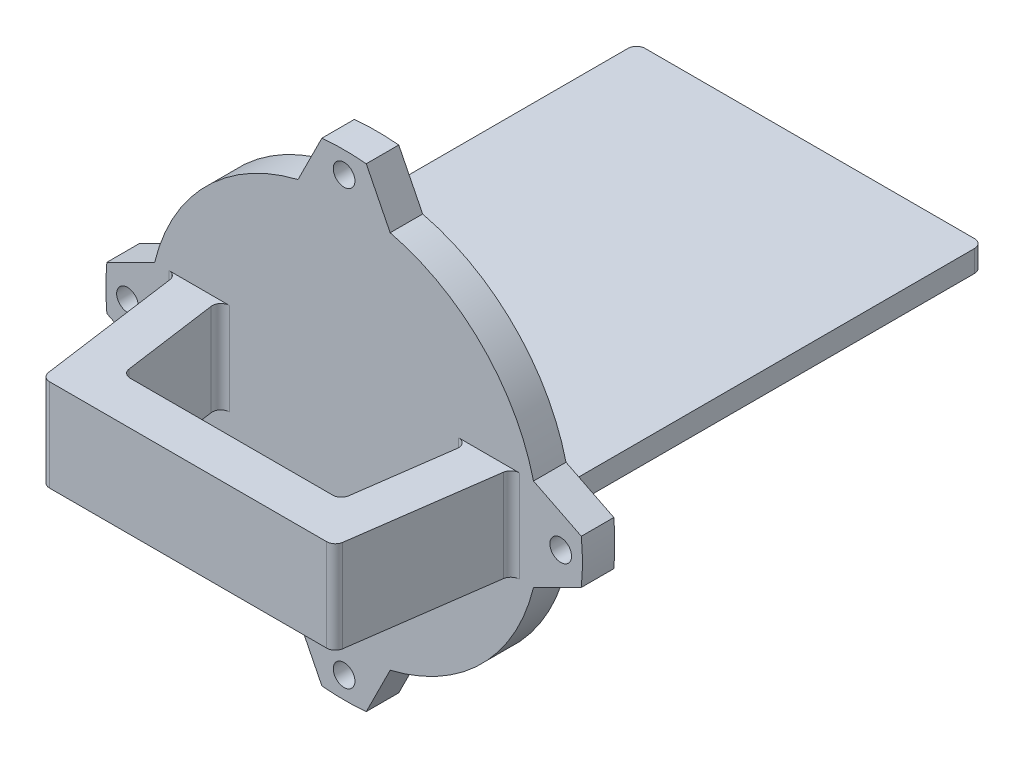
SolidWorks part; units mm, degrees
note: The reader was unsure of these and kept them because the rebuilt part matched: shared geometry of "Sketch4<86>", "Sketch9<5>".
ref_plane "Front Plane" through (0, 0, 0) normal (0, 0, 1) x (1, 0, 0)
ref_plane "Top Plane" through (0, 0, 0) normal (0, 1, 0) x (1, 0, 0)
ref_plane "Right Plane" through (0, 0, 0) normal (1, 0, 0) x (0, 0, -1)
sketch "Sketch2" plane through (0, 0, 0) normal (0, 0, 1) x (1, 0, 0)
  line L0 (6.5016, 69.5468) -> (13.5099, 55.5302)
  line L1 (-69.5468, -6.5016) -> (-55.5302, -13.5099)
  line L2 (-69.5468, 6.5016) -> (-55.5302, 13.5099)
  line L3 (-6.5016, 69.5468) -> (-13.5099, 55.5302)
  line L4 (69.5468, -6.5016) -> (55.5302, -13.5099)
  line L5 (69.5468, 6.5016) -> (55.5302, 13.5099)
  line L6 (-6.5016, -69.5468) -> (-13.5099, -55.5302)
  line L7 (6.5016, -69.5468) -> (13.5099, -55.5302)
  arc A0 (-55.5302, -13.5099) -> (-13.5099, -55.5302) centre (0, 0) ccw
  arc A1 (-6.5016, -69.5468) -> (6.5016, -69.5468) centre (0, 0) ccw
  arc A2 (-69.5468, 6.5016) -> (-69.5468, -6.5016) centre (0, 0) ccw
  arc A3 (6.5016, 69.5468) -> (-6.5016, 69.5468) centre (0, 0) ccw
  arc A4 (69.5468, -6.5016) -> (69.5468, 6.5016) centre (0, 0) ccw
  circle A5 centre (-63.5, 0) radius 3.175
  circle A6 centre (0, 63.5) radius 3.175
  circle A7 centre (63.5, 0) radius 3.175
  circle A8 centre (0, -63.5) radius 3.175
  arc A9 (-13.5099, 55.5302) -> (-55.5302, 13.5099) centre (0, 0) ccw
  arc A10 (55.5302, 13.5099) -> (13.5099, 55.5302) centre (0, 0) ccw
  arc A11 (13.5099, -55.5302) -> (55.5302, -13.5099) centre (0, 0) ccw
  point P23 (0, 0)
  point P31 (0, 0)
  dimension "D1" = 4
  dimension "D2" = 4
extrude "Boss-Extrude1" add sketch "Sketch2" along normal blind 9.525
sketch "Sketch4" plane through (0, 0, 9.525) normal (0, 0, 1) x (1, 0, 0)
  line L1 (49.1802, 13.5099) -> (36.4802, 13.5099)
  line L2 (36.4802, -13.5099) -> (36.4802, 13.5099)
  line L3 (49.1802, -13.5099) -> (36.4802, -13.5099)
  line L4 (-49.1802, -13.5099) -> (-36.4802, -13.5099)
  line L5 (-49.1802, -13.5099) -> (-49.1802, 13.5099)
  line L6 (-49.1802, 13.5099) -> (-36.4802, 13.5099)
  line L7 (-36.4802, -13.5099) -> (-36.4802, 13.5099)
  line L8 (49.1802, -13.5099) -> (49.1802, 13.5099)
ref_plane "Plane1" through (0, 0, 55.245) normal (0, 0, 1) x (1, 0, 0)
sketch "Sketch9" plane through (0, 0, 55.245) normal (0, 0, 1) x (1, 0, 0)
  line L1 (-49.1802, 13.5099) -> (-36.4802, 13.5099) construction
  line L2 (42.8302, -13.5099) -> (30.1302, -13.5099)
  line L3 (-42.8302, 13.5099) -> (-30.1302, 13.5099)
  line L4 (-42.8302, 13.5099) -> (-42.8302, -13.5099)
  line L5 (-42.8302, -13.5099) -> (-30.1302, -13.5099)
  line L6 (-30.1302, 13.5099) -> (-30.1302, -13.5099)
  line L7 (30.1302, 13.5099) -> (30.1302, -13.5099)
  line L8 (42.8302, 13.5099) -> (30.1302, 13.5099)
  line L9 (42.8302, 13.5099) -> (42.8302, -13.5099)
loft "Loft5" add section "Sketch4" section "Sketch9"
loft "Loft6" add section "Sketch4<86>" section "Sketch9<5>"
sketch "Sketch4<86>" plane through (0, 0, 9.525) normal (0, 0, 1) x (1, 0, 0) same geometry as "Sketch4"
sketch "Sketch9<5>" plane through (0, 0, 55.245) normal (0, 0, 1) x (1, 0, 0) same geometry as "Sketch9"
sketch "Sketch11" plane through (0, 0, 55.245) normal (0, 0, 1) x (1, 0, 0)
  line L1 (-42.8302, 13.5099) -> (42.8302, 13.5099)
  line L2 (-42.8302, 13.5099) -> (-42.8302, -13.5099)
  line L3 (-42.8302, -13.5099) -> (42.8302, -13.5099)
  line L4 (42.8302, 13.5099) -> (42.8302, -13.5099)
extrude "Boss-Extrude3" add sketch "Sketch11" against normal blind 12.7
fillet "Fillet2" radius 2.54 18 edges at (-31.8941, 0, 42.545) (31.8941, 0, 42.545)
sketch "Sketch12" plane through (0, 0, 0) normal (0, 0, -1) x (-1, 0, 0)
  line L0 (-50.8, 0) -> (50.8, 0) construction
  line L2 (-50.8, 3.175) -> (50.8, 3.175)
  line L4 (-50.8, 3.175) -> (-50.8, -3.175)
  line L5 (-50.8, -3.175) -> (50.8, -3.175)
  line L6 (50.8, 3.175) -> (50.8, -3.175)
  dimension "D1" = 6.35
  dimension "D2" = 0
extrude "Boss-Extrude4" add sketch "Sketch12" along normal blind 127
fillet "Fillet4" radius 2.54 4 edges at (-50.8, 0, 0) (-50.8, 0, -127) (50.8, 0, -127) (50.8, 0, 0)
